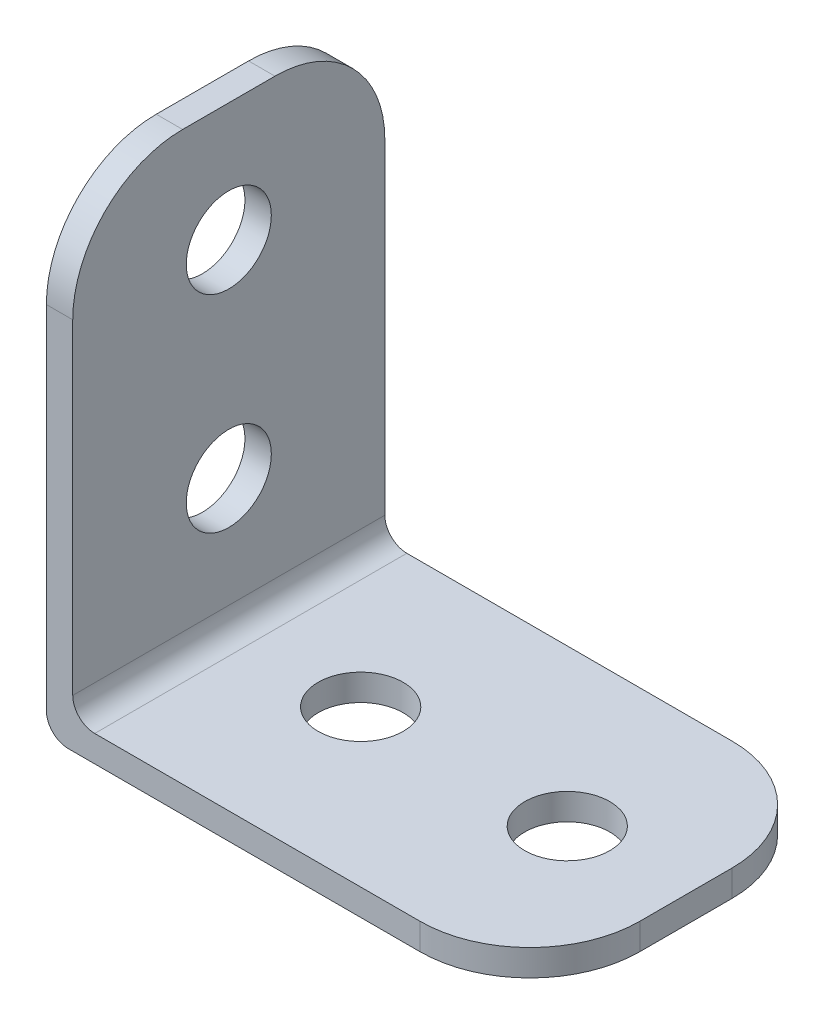
SolidWorks part; units mm, degrees
ref_plane "Front Plane" through (0, 0, 0) normal (0, 0, 1) x (1, 0, 0)
ref_plane "Top Plane" through (0, 0, 0) normal (0, 1, 0) x (1, 0, 0)
ref_plane "Right Plane" through (0, 0, 0) normal (1, 0, 0) x (0, 0, -1)
sketch "Sketch1" plane through (0, 0, 0) normal (0, 1, 0) x (1, 0, 0)
  line L0 (-11.4727, 9.1222) -> (-11.4727, -8.9118)
  line L1 (-12.9967, 9.1222) -> (14.9433, 9.1222)
  line L2 (-12.9967, 9.1222) -> (-12.9967, -8.9118)
  line L3 (-12.9967, -8.9118) -> (14.9433, -8.9118)
  line L4 (14.9433, 9.1222) -> (14.9433, -8.9118)
  dimension "D1" = 18.034
  dimension "D2" = 27.94
  dimension "D3" = 1.524
extrude "Boss-Extrude2" add sketch "Sketch1" along normal blind 1.524 contours L4 L1 L0 L3 region at (1.7353, 0, -0.1052)
extrude "Boss-Extrude3" add sketch "Sketch1<4>" along normal blind 27.94 contours L2 L3 L0 L1 region at (-12.2347, 0, -0.1052)
sketch "Sketch1<4>" plane through (0, 0, 0) normal (0, 1, 0) x (1, 0, 0) same geometry as "Sketch1"
fillet "Fillet1" radius 1.27 2 edges at (-12.9967, 0, -0.1052) (-11.4727, 1.524, -0.1052)
fillet "Fillet2" radius 6.35 4 edges at (-12.2347, 27.94, 8.9118) (-12.2347, 27.94, -9.1222) (14.9433, 0.762, -9.1222) (14.9433, 0.762, 8.9118)
sketch "Sketch2" plane through (0, 1.524, 0) normal (0, 1, 0) x (1, 0, 0)
  line L0 (-11.4727, 0.1052) -> (14.9433, 0.1052) construction
  line L1 (-11.4727, 2.7722) -> (-11.4727, -2.5618) construction
  line L2 (14.9433, 2.7722) -> (14.9433, -2.5618) construction
  point P6 (-6.3927, 0.1052)
  point P7 (-3.8527, 0.1052)
  point P8 (8.0853, 0.1052)
  dimension "D1" = 5.08
  dimension "D2" = 2.54
  dimension "D3" = 11.938
hole_wizard "#10 (0.1935) Diameter Hole1" positions "Sketch5" profile "Sketch6" hole size "#10" standard "ANSI Inch"
sketch "Sketch5" plane through (0, 1.524, 0) normal (0, 1, 0) x (1, 0, 0)
  point P0 (-3.8527, 0.1052)
  point P3 (8.0853, 0.1052)
sketch "Sketch6" plane through (-3.8527, 1.524, -0.1052) normal (1, 0, 0) x (0, 0, 1)
  line L0 (0, 0) -> (0, 6.5566)
  line L1 (0, 6.5566) -> (2.4574, 5.08)
  line L2 (2.4574, 5.08) -> (2.4574, 0)
  line L5 (2.4574, 0) -> (0, 0)
  line L10 (0, 6.5566) -> (-2.4575, 5.08) construction
  line L11 (0, -6.35) -> (0, 107.95) construction
  dimension "Hole Dia." = 4.9149
  dimension "Hole Depth" = 5.08
  dimension "Drill Angle" = 118
sketch "Sketch7" plane through (-11.4727, 0, 0) normal (1, 0, 0) x (0, 0, -1)
  line L0 (0.1052, 1.524) -> (0.1052, 27.94) construction
  line L1 (2.7722, 27.94) -> (-2.5618, 27.94) construction
  point P5 (0.1052, 6.604)
  point P6 (0.1052, 9.144)
  point P7 (0.1052, 21.082)
  dimension "D1" = 5.08
  dimension "D2" = 2.54
  dimension "D3" = 11.938
hole_wizard "#10 (0.1935) Diameter Hole2" positions "Sketch8" profile "Sketch9" hole size "#10" standard "ANSI Inch"
sketch "Sketch8" plane through (-11.4727, 0, 0) normal (1, 0, 0) x (0, 0, -1)
  point P0 (0.1052, 9.144)
  point P3 (0.1052, 21.082)
sketch "Sketch9" plane through (-11.4727, 9.144, -0.1052) normal (0, 1, 0) x (0, 0, -1)
  line L0 (0, 0) -> (0, 6.5566)
  line L1 (0, 6.5566) -> (2.4574, 5.08)
  line L2 (2.4574, 5.08) -> (2.4574, 0)
  line L5 (2.4574, 0) -> (0, 0)
  line L10 (0, 6.5566) -> (-2.4574, 5.08) construction
  line L11 (0, -6.35) -> (0, 107.95) construction
  dimension "Hole Dia." = 4.9149
  dimension "Hole Depth" = 5.08
  dimension "Drill Angle" = 118
